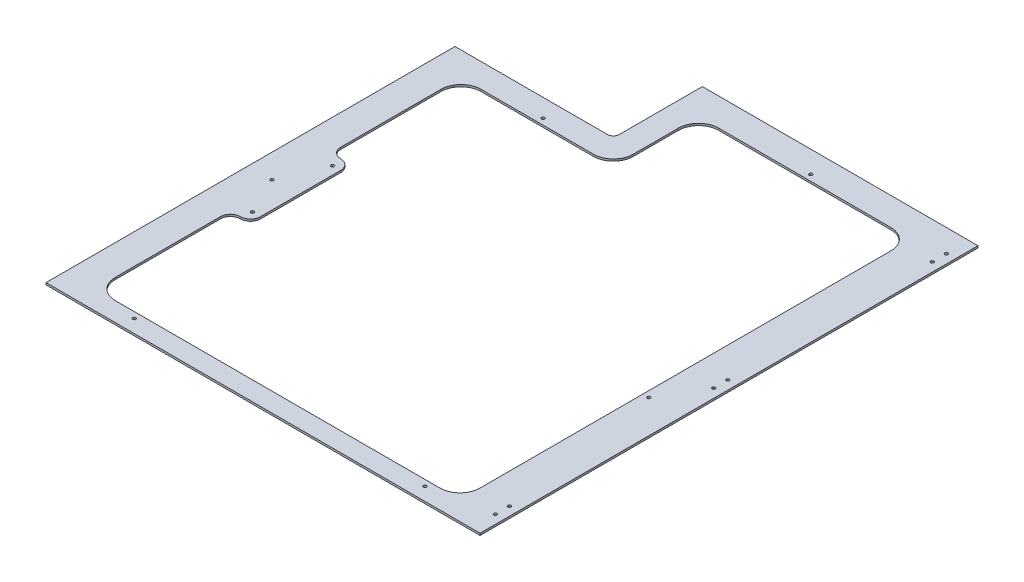
SolidWorks part; units mm, degrees
ref_plane "Alzado" through (0, 0, 0) normal (0, 0, 1) x (1, 0, 0)
ref_plane "Planta" through (0, 0, 0) normal (0, 1, 0) x (1, 0, 0)
ref_plane "Vista lateral" through (0, 0, 0) normal (1, 0, 0) x (0, 0, -1)
sketch "Croquis1" plane through (0, 0, 0) normal (0, 1, 0) x (1, 0, 0)
  line L1 (0, 0) -> (434, 0)
  line L2 (0, 0) -> (0, 500)
  line L3 (0, 500) -> (434, 500)
  line L4 (434, 0) -> (434, 500)
  dimension "D1" = 500
  dimension "D2" = 434
extrude "Saliente-Extruir1" add sketch "Croquis1" along normal blind 2
sketch "Croquis3" plane through (0, 0, 0) normal (0, -1, 0) x (1, 0, 0)
  line L1 (0, -500) -> (157, -500)
  line L2 (0, -500) -> (0, -410)
  line L3 (0, -410) -> (157, -410)
  line L4 (157, -500) -> (157, -410)
  dimension "D1" = 90
  dimension "157" = 157
extrude "Cortar-Extruir2" cut sketch "Croquis3" against normal up to surface (2 mm away) up to face at (217, 2, -250)
fillet "Redondeo1" radius 5 1 edges at (157, 1, -410)
sketch "Croquis4" plane through (0, 0, 0) normal (0, -1, 0) x (1, 0, 0)
  line L0 (434, 0) -> (434, -500) construction
  line L1 (30, -20) -> (394, -20)
  line L2 (30, -20) -> (30, -385)
  line L3 (30, -385) -> (182, -385)
  line L4 (394, -20) -> (394, -233.6615)
  line L6 (182, -385) -> (182, -470)
  line L7 (182, -470) -> (394, -470)
  line L8 (394, -233.6615) -> (394, -470)
  line L9 (434, -500) -> (157, -500) construction
  line L10 (0, 0) -> (434, 0) construction
  line L11 (0, -410) -> (0, 0) construction
  line L12 (152, -410) -> (0, -410) construction
  line L13 (157, -500) -> (157, -415) construction
  dimension "D1" = 40
  dimension "D2" = 30
  dimension "D3" = 20
  dimension "D4" = 30
  dimension "D5" = 25
  dimension "D6" = 25
extrude "Cortar-Extruir3" cut sketch "Croquis4" against normal up to surface (2 mm away) up to face at (190.7194, 2, -319.1378)
fillet "Redondeo2" radius 20 6 edges at (30, 1, -385) (182, 1, -385) (182, 1, -470) (394, 1, -470) (394, 1, -20) (30, 1, -20)
sketch "Croquis6" plane through (0, 0, 0) normal (0, -1, 0) x (1, 0, 0)
  line L0 (374, -20) -> (50, -20) construction
  line L1 (0, -410) -> (0, 0) construction
  line L2 (288, -470) -> (288, -243.2159) construction
  line L3 (202, -470) -> (374, -470) construction
  line L4 (106, -385) -> (106, -410) construction
  line L5 (30, -202.5) -> (394, -202.5) construction
  line L6 (30, -40) -> (30, -365) construction
  line L7 (394, -450) -> (394, -40) construction
  line L8 (50, -385) -> (162, -385) construction
  line L9 (152, -410) -> (0, -410) construction
  circle A0 centre (75, -14) radius 1.55
  circle A1 centre (365, -14) radius 1.55
  circle A2 centre (288, -476) radius 1.55
  circle A5 centre (106, -391) radius 1.55
  circle A6 centre (24, -202.5) radius 1.55
  circle A7 centre (400, -202.5) radius 1.55
  dimension "D1" = 3.1
  dimension "D5" = 3.1
  dimension "D2" = 6
  dimension "D3" = 290
  dimension "D4" = 75
  dimension "D6" = 6
  dimension "D7" = 6
  dimension "D8" = 6
  dimension "D9" = 6
extrude "Cortar-Extruir5" cut sketch "Croquis6" against normal up to surface (2 mm away) up to face at (202, 2, -291.6667)
sketch "Croquis7" plane through (0, 0, 0) normal (0, -1, 0) x (1, 0, 0)
  line L0 (0, 0) -> (434, 0) construction
  line L2 (434, 0) -> (434, -500) construction
  line L3 (434, -500) -> (157, -500) construction
  line L4 (434, -250) -> (394, -250) construction
  line L5 (394, -450) -> (394, -40) construction
  circle A0 centre (424.25, -25) radius 1.55
  circle A1 centre (424.25, -39) radius 1.55
  circle A2 centre (424.25, -475) radius 1.55
  circle A3 centre (424.25, -461) radius 1.55
  circle A4 centre (424.25, -243) radius 1.55
  circle A5 centre (424.25, -257) radius 1.55
  dimension "D1" = 3.1
  dimension "D2" = 14
  dimension "D3" = 25
  dimension "D4" = 9.75
  dimension "D5" = 14
  dimension "D6" = 9.75
  dimension "D7" = 25
  dimension "D8" = 7
  dimension "D9" = 7
extrude "Cortar-Extruir6" cut sketch "Croquis7" against normal up to surface (2 mm away) up to face at (400, 2, -204.05)
sketch "Croquis8" plane through (0, 0, 0) normal (0, -1, 0) x (1, 0, 0)
  line L0 (0, -205) -> (136.8226, -205) construction
  line L1 (0, -410) -> (0, 0) construction
  line L2 (30, -40) -> (30, -365) construction
  line L3 (30, -155) -> (50, -155)
  line L4 (30, -155) -> (30, -255)
  line L5 (30, -255) -> (50, -255)
  line L6 (50, -155) -> (50, -255)
  dimension "D1" = 100
  dimension "D2" = 50
  dimension "D3" = 20
extrude "Saliente-Extruir2" add sketch "Croquis8" against normal up to surface (2 mm away) up to face at (424.25, 2, -26.55)
fillet "Redondeo3" radius 10 4 edges at (30, 1, -255) (50, 1, -255) (50, 1, -155) (30, 1, -155)
sketch "Croquis9" plane through (0, 0, 0) normal (0, -1, 0) x (1, 0, 0)
  line L0 (0, -205) -> (50, -205) construction
  line L1 (0, -410) -> (0, 0) construction
  line L2 (50, -245) -> (50, -165) construction
  circle A0 centre (42, -165) radius 1.55
  circle A1 centre (42, -245) radius 1.55
  dimension "D2" = 3.1
  dimension "D1" = 40
  dimension "D3" = 40
  dimension "D4" = 8
  dimension "D5" = 8
extrude "Cortar-Extruir7" cut sketch "Croquis9" against normal up to surface (2 mm away) up to face at (424.25, 2, -26.55)
sketch "Croquis10" plane through (0, 0, 0) normal (0, -1, 0) x (1, 0, 0)
  line L12 (1, -409) -> (152, -409)
  line L13 (158, -415) -> (158, -499)
  line L14 (158, -499) -> (433, -499)
  line L15 (433, -499) -> (433, -1)
  line L16 (433, -1) -> (1, -1)
  line L17 (1, -1) -> (1, -409)
  line L18 (1, -409) -> (152, -409)
  line L19 (158, -415) -> (158, -499)
  line L20 (158, -499) -> (433, -499)
  line L21 (433, -499) -> (433, -1)
  line L22 (433, -1) -> (1, -1)
  line L23 (1, -1) -> (1, -409)
  arc A2 (158, -415) -> (152, -409) centre (152, -415) ccw
  arc A3 (158, -415) -> (152, -409) centre (152, -415) ccw
  dimension "D1" = 1
extrude "Cortar-Extruir8" cut sketch "Croquis10" against normal blind 10 flip side to cut
sketch "Croquis11" plane through (0, 0, 0) normal (0, -1, 0) x (1, 0, 0)
  line L0 (433, -499) -> (433, -1) construction
  line L1 (158, -499) -> (433, -499)
  line L2 (158, -499) -> (158, -497.75)
  line L3 (158, -497.75) -> (433, -497.75)
  line L4 (433, -499) -> (433, -497.75)
  dimension "D1" = 1.25
extrude "Cortar-Extruir9" cut sketch "Croquis11" against normal up to surface (2 mm away) up to face at (148, 2, -262.7778)
sketch "Croquis12" plane through (0, 0, 0) normal (0, -1, 0) x (1, 0, 0)
  line L1 (1, -1) -> (0, -1)
  line L2 (1, -1) -> (1, -409)
  line L3 (1, -409) -> (0, -409)
  line L4 (0, -1) -> (0, -409)
  dimension "D1" = 1
extrude "Saliente-Extruir3" add sketch "Croquis12" against normal up to surface (2 mm away) up to face at (148, 2, -262.7778)
sketch "Croquis13" plane through (0, 0, 0) normal (0, -1, 0) x (1, 0, 0)
  line L0 (394, -450) -> (394, -40) construction
  line L1 (202, -470) -> (374, -470) construction
  line L2 (182, -405) -> (182, -450) construction
  line L3 (50, -385) -> (162, -385) construction
  line L4 (30, -265) -> (30, -365) construction
  line L5 (50, -245) -> (50, -165) construction
  line L6 (30, -40) -> (30, -145) construction
  line L7 (374, -20) -> (50, -20) construction
  line L8 (394, -450) -> (394, -40)
  line L9 (202, -470) -> (374, -470)
  line L10 (182, -405) -> (182, -450)
  line L11 (50, -385) -> (162, -385)
  line L12 (30, -265) -> (30, -365)
  line L13 (50, -245) -> (50, -165)
  line L14 (30, -40) -> (30, -145)
  line L15 (374, -20) -> (50, -20)
  line L16 (374, -5) -> (50, -5)
  line L17 (15, -40) -> (15, -145)
  line L18 (167, -405) -> (167, -450) construction
  line L19 (15, -265) -> (15, -365)
  line L20 (50, -400) -> (154, -400)
  line L21 (167, -413) -> (167, -450)
  line L22 (202, -485) -> (374, -485)
  line L23 (409, -450) -> (409, -40)
  line L24 (15, -145) -> (15, -265)
  line L25 (50, -400) -> (162, -400) construction
  line L26 (35, -240.5051) -> (35, -169.4949) construction
  arc A0 (394, -40) -> (374, -20) centre (374, -40) ccw construction
  arc A1 (374, -470) -> (394, -450) centre (374, -450) ccw construction
  arc A2 (182, -450) -> (202, -470) centre (202, -450) ccw construction
  arc A3 (182, -405) -> (162, -385) centre (162, -405) ccw construction
  arc A4 (30, -365) -> (50, -385) centre (50, -365) ccw construction
  arc A5 (40, -255) -> (30, -265) centre (40, -265) ccw construction
  arc A6 (40, -255) -> (50, -245) centre (40, -245) ccw construction
  arc A7 (50, -165) -> (40, -155) centre (40, -165) ccw construction
  arc A8 (30, -145) -> (40, -155) centre (40, -145) ccw construction
  arc A9 (50, -20) -> (30, -40) centre (50, -40) ccw construction
  arc A10 (394, -40) -> (374, -20) centre (374, -40) ccw
  arc A11 (374, -470) -> (394, -450) centre (374, -450) ccw
  arc A12 (182, -450) -> (202, -470) centre (202, -450) ccw
  arc A13 (182, -405) -> (162, -385) centre (162, -405) ccw
  arc A14 (30, -365) -> (50, -385) centre (50, -365) ccw
  arc A15 (40, -255) -> (30, -265) centre (40, -265) ccw
  arc A16 (40, -255) -> (50, -245) centre (40, -245) ccw
  arc A17 (50, -165) -> (40, -155) centre (40, -165) ccw
  arc A18 (30, -145) -> (40, -155) centre (40, -145) ccw
  arc A19 (50, -20) -> (30, -40) centre (50, -40) ccw
  arc A20 (50, -5) -> (15, -40) centre (50, -40) ccw
  circle A21 centre (42, -165) radius 5
  arc A22 (35, -169.4949) -> (35, -169.4949) centre (35, -169.4949) ccw
  arc A23 (35, -240.5051) -> (35, -240.5051) centre (35, -240.5051) ccw
  circle A24 centre (42, -245) radius 5
  arc A25 (15, -365) -> (50, -400) centre (50, -365) ccw
  arc A27 (167, -450) -> (202, -485) centre (202, -450) ccw
  arc A28 (374, -485) -> (409, -450) centre (374, -450) ccw
  arc A29 (409, -40) -> (374, -5) centre (374, -40) ccw
  arc A30 (15, -145) -> (35, -169.4949) centre (40, -145) ccw construction
  arc A31 (35, -240.5051) -> (15, -265) centre (40, -265) ccw construction
  circle A32 centre (24, -202.5) radius 2.25
  circle A33 centre (75, -14) radius 2.25
  circle A34 centre (365, -14) radius 2.25
  circle A35 centre (400, -202.5) radius 2.25
  circle A36 centre (288, -476) radius 2.25
  circle A37 centre (106, -391) radius 2.25
  arc A38 (168.1765, -408.2941) -> (158.7059, -398.8235) centre (162, -405) ccw
  arc A39 (167, -405) -> (162, -400) centre (162, -405) ccw construction
  arc A40 (168.1765, -408.2941) -> (167, -413) centre (177, -413) ccw
  arc A41 (158.7059, -398.8235) -> (154, -400) centre (154, -390) cw
  dimension "D2" = 10
  dimension "D3" = 10
  dimension "D4" = 4.5
  dimension "D5" = 14
  dimension "D6" = 10
  dimension "D1" = 15
